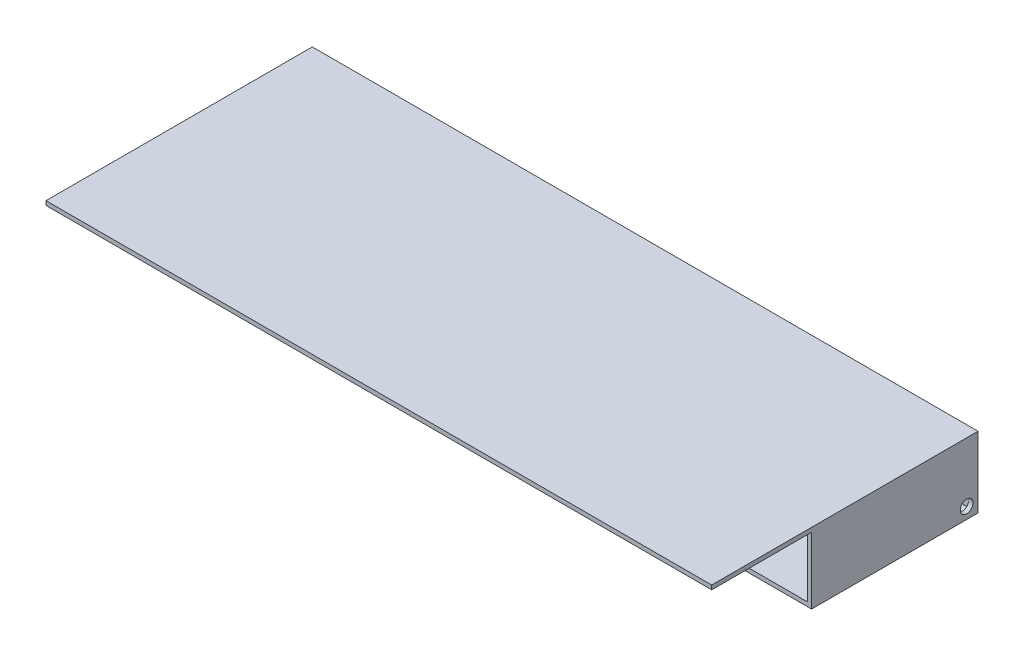
SolidWorks part; units mm, degrees
ref_plane "Front Plane" through (0, 0, 0) normal (0, 0, 1) x (1, 0, 0)
ref_plane "Top Plane" through (0, 0, 0) normal (0, 1, 0) x (1, 0, 0)
ref_plane "Right Plane" through (0, 0, 0) normal (1, 0, 0) x (0, 0, -1)
sketch "Sketch1" plane through (0, 0, 0) normal (0, 1, 0) x (1, 0, 0)
  line L1 (1000, -400) -> (-1000, -400)
  line L2 (1000, -400) -> (1000, 400)
  line L3 (1000, 400) -> (-1000, 400)
  line L4 (-1000, -400) -> (-1000, 400)
  line L5 (1000, -400) -> (-1000, 400) construction
  line L6 (1000, 400) -> (-1000, -400) construction
  point P0 (0, 0)
  dimension "D1" = 2000
  dimension "D2" = 800
extrude "Boss-Extrude1" add sketch "Sketch1" along normal blind 12.7 contours L4 L3 L2 L1
sketch "Sketch2" plane through (0, 0, 0) normal (0, -1, 0) x (1, 0, 0)
  line L0 (1000, 400) -> (1000, -400) construction
  line L1 (-1000, -400) -> (1000, -400)
  line L2 (-1000, -400) -> (-1000, 100)
  line L3 (-1000, 100) -> (1000, 100)
  line L4 (1000, -400) -> (1000, 100)
  dimension "D1" = 500
extrude "Boss-Extrude2" add sketch "Sketch2" along normal blind 200
shell "Shell1" thickness 12.7 removed face at (0, -100, 100)
sketch "Sketch4" plane through (0, 0, -387.3) normal (0, 0, 1) x (1, 0, 0)
  line L0 (0, 0) -> (0, -187.3) construction
  line L1 (987.3, -187.3) -> (-987.3, -187.3) construction
  line L2 (987.3, 0) -> (-987.3, 0) construction
  line L3 (12.7, -187.3) -> (-12.7, -187.3)
  line L4 (12.7, -187.3) -> (12.7, 0)
  line L5 (12.7, 0) -> (-12.7, 0)
  line L6 (-12.7, -187.3) -> (-12.7, 0)
  line L7 (12.7, -187.3) -> (-12.7, 0) construction
  line L8 (12.7, 0) -> (-12.7, -187.3) construction
  point P5 (0, -93.65)
  dimension "D1" = 25.4
extrude "Boss-Extrude3" add sketch "Sketch4" along normal up to surface (487.3 mm away) up to face at (0, -96.825, 100)
sketch "Sketch5" plane through (-1000, 0, 0) normal (-1, 0, 0) x (0, 0, 1)
  line L0 (-365.71, -184.76) -> (-365.71, -200) construction
  line L1 (100, -200) -> (-400, -200) construction
  line L2 (-384.76, -165.71) -> (-400, -165.71) construction
  line L3 (-400, 12.7) -> (-400, -200) construction
  circle A0 centre (-365.71, -165.71) radius 19.05
  dimension "D2" = 38.1
  dimension "D1" = 15.24
  dimension "D3" = 15.24
extrude "Cut-Extrude1" cut sketch "Sketch5" against normal up to surface (2000 mm away) up to face at (1000, -62.4333, 33.3333)
sketch "Sketch6" plane through (0, 12.7, 0) normal (0, 1, 0) x (1, 0, 0)
  line L0 (-993.65, 400) -> (-993.65, -400) construction
  line L1 (1000, 400) -> (-1000, 400) construction
  line L2 (1000, -400) -> (-1000, -400) construction
  line L3 (-1000, -400) -> (-1000, 400) construction
  line L4 (-1000, -100) -> (-993.65, -100) construction
  line L5 (993.65, 400) -> (993.65, -400) construction
  line L6 (993.65, -100) -> (1000, -100) construction
  line L7 (1000, -400) -> (1000, 400) construction
  circle A0 centre (-993.65, 150) radius 1.7797
  circle A1 centre (-993.65, 275) radius 3.0468
  circle A2 centre (-993.65, 25) radius 4.5871
  circle A3 centre (-993.65, -74.6) radius 4.3943
  circle A4 centre (993.65, 275) radius 4.1035
  circle A5 centre (993.65, 150) radius 4.1035
  circle A6 centre (993.65, 25) radius 3.2829
  circle A7 centre (993.65, -74.6) radius 5.1599
  dimension "D1" = 6.35
  dimension "D2" = 500
  dimension "D3" = 500
  dimension "D4" = 6.35
  dimension "D5" = 125
  dimension "D6" = 250
  dimension "D7" = 375
  dimension "D8" = 474.6
  dimension "D9" = 250
  dimension "D10" = 125
  dimension "D11" = 375
  dimension "D12" = 474.6
